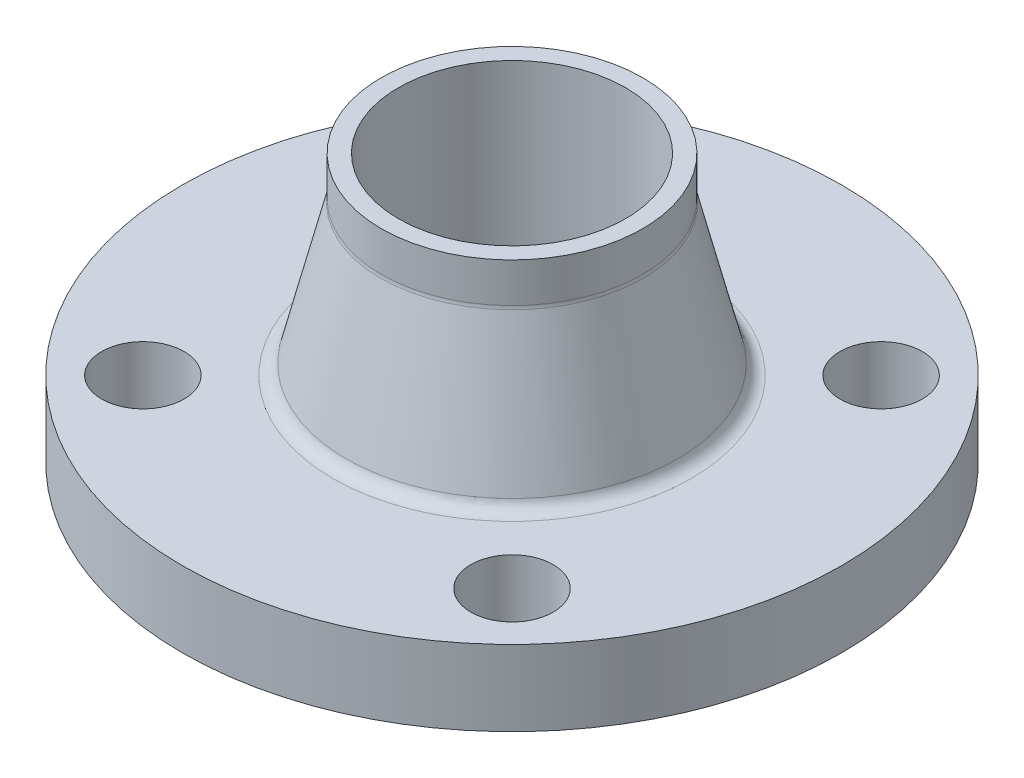
SolidWorks part; units mm, degrees
material "Cast Alloy Steel"
ref_plane "Plane1" through (0, 0, 0) normal (0, 0, 1) x (1, 0, 0)
ref_plane "Plane2" through (0, 0, 0) normal (0, 1, 0) x (1, 0, 0)
ref_plane "Plane3" through (0, 0, 0) normal (1, 0, 0) x (0, 0, -1)
sketch "Sketch3" plane through (0, 0, 0) normal (0, 0, 1) x (1, 0, 0)
  line L0 (0, 0) -> (0, 68.58) construction
  line L1 (26.2509, 61.9125) -> (26.2509, -1.5875)
  line L2 (26.2509, -1.5875) -> (46.0375, -1.5875)
  line L3 (46.0375, -1.5875) -> (46.0375, 0)
  line L4 (46.0375, 0) -> (76.2, 0)
  line L5 (76.2, 0) -> (76.2, 17.4625)
  line L6 (76.2, 17.4625) -> (41.3771, 17.4625)
  line L7 (38.2956, 19.8727) -> (30.3195, 52.0108)
  line L8 (30.226, 52.7756) -> (30.226, 61.9125)
  line L10 (30.226, 61.9125) -> (26.2509, 61.9125)
  line L11 (41.3771, 17.4625) -> (38.8937, 17.4625) construction
  line L12 (37.7455, 22.0893) -> (38.8937, 17.4625) construction
  arc A0 (41.3771, 17.4625) -> (38.2956, 19.8727) centre (41.3771, 20.6375) cw
  arc A1 (30.3195, 52.0108) -> (30.226, 52.7756) centre (33.401, 52.7756) cw
  point P18 (30.226, 52.3875)
  dimension "D3" = 9.525
revolve "Base-Revolve" add sketch "Sketch3" angle 360 about L0
sketch "Sketch4" plane through (0, 17.4625, 0) normal (0, 1, 0) x (-1, 0, 0)
  line L0 (-87.63, 0) -> (93.98, 0) construction
  line L1 (0, -100.33) -> (0, 93.98) construction
  line L2 (-42.6562, 42.6562) -> (0, 0) construction
  line L3 (0, 0) -> (62.23, 62.23) construction
  circle A0 centre (-42.6562, 42.6562) radius 9.525
  dimension "Bolt Hole Dia" = 19.05
  dimension "Bolt Hole Angle" = 45
  dimension "Bolt Circle Dia" = 120.65
extrude "1st Bolt Hole" cut sketch "Sketch4" against normal through all
ref_axis "Axis1" through (0, 0, 0) along (0, 1, 0)
pattern_circular "Bolt Hole Pattern" count 4 over 360 about axis through (0, 0, 0) along (0, 1, 0) of "1st Bolt Hole"
ref_plane "CP Offset Plane" through (0, 63.5, 0) normal (0, 1, 0) x (-1, 0, 0)
sketch "CP Sketch Point" plane through (0, 63.5, 0) normal (0, 1, 0) x (-1, 0, 0)
  point P0 (0, 0)
other "CPoint1" parameters "Diameter"=50.8
ref_axis "Axis2" through (0, 73.5, 0) along (0, -1, 0)
ref_axis "Mate Axis" through (42.6562, 17.4625, 42.6562) along (0, -1, 0)
ref_plane "Mate Plane" through (0, 17.4625, 0) normal (0, 1, 0) x (-1, 0, 0)
equation "\"D3@Sketch3\"=\"Q@Sketch3\"/2"
